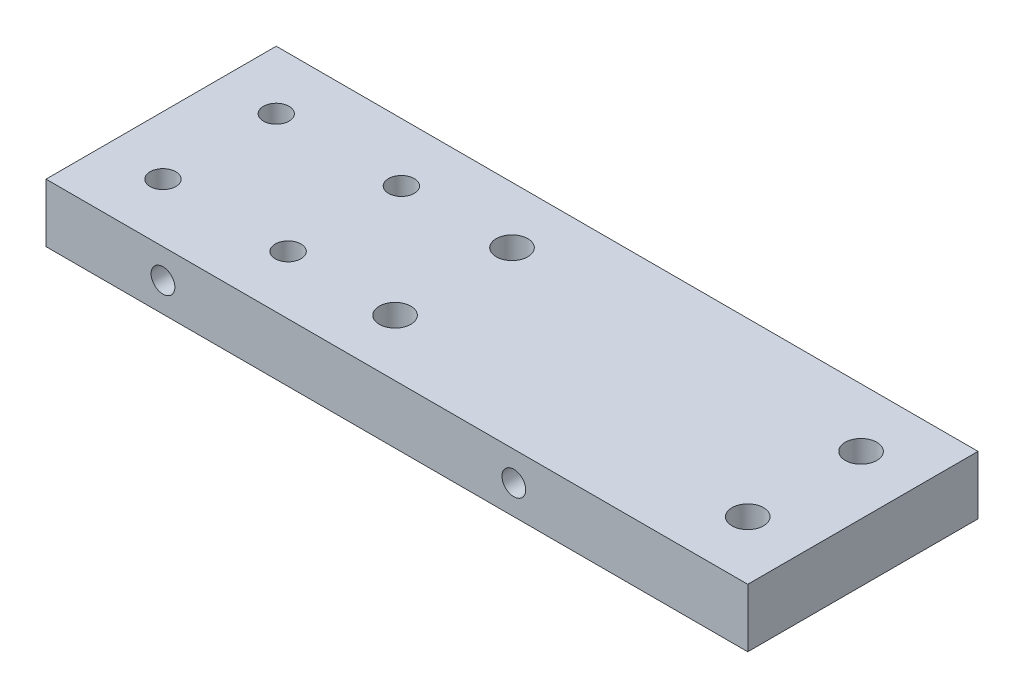
SolidWorks part; units mm, degrees
material "6061 Alloy"
ref_plane "Front Plane" through (0, 0, 0) normal (0, 0, 1) x (1, 0, 0)
ref_plane "Top Plane" through (0, 0, 0) normal (0, 1, 0) x (1, 0, 0)
ref_plane "Right Plane" through (0, 0, 0) normal (1, 0, 0) x (0, 0, -1)
sketch "Sketch1" plane through (0, 0, 0) normal (0, 1, 0) x (1, 0, 0)
  line L1 (-76.2, 25) -> (76.2, 25)
  line L2 (-76.2, 25) -> (-76.2, -25)
  line L3 (-76.2, -25) -> (76.2, -25)
  line L4 (76.2, 25) -> (76.2, -25)
  line L5 (-76.2, 25) -> (76.2, -25) construction
  line L6 (-76.2, -25) -> (76.2, 25) construction
  point P0 (0, 0)
  dimension "D1" = 50
  dimension "D2" = 152.4
extrude "Boss-Extrude1" add sketch "Sketch1" along normal blind 12.7
sketch "Sketch3" plane through (0, 0, 0) normal (0, -1, 0) x (1, 0, 0)
  line L0 (0, 0) -> (0, -20.7585) construction
  line L1 (0, 0) -> (-13.1006, 0) construction
  line L2 (-76.2, -25) -> (-76.2, 25) construction
  line L3 (-76.2, 25) -> (76.2, 25) construction
  line L4 (76.2, -25) -> (-76.2, -25) construction
  circle A0 centre (-63.5, 12.3) radius 2.794
  circle A1 centre (-63.5, -12.3) radius 2.794
  circle A2 centre (63.5, 12.3) radius 3.429
  circle A3 centre (63.5, -12.3) radius 3.429
  circle A4 centre (-12.699, 12.7) radius 3.429
  circle A5 centre (-12.699, -12.7) radius 3.429
  circle A6 centre (-36.322, 12.3) radius 2.794
  circle A7 centre (-36.322, -12.3) radius 2.794
  dimension "D1" = 12.7
  dimension "D4" = 76.2
  dimension "D5" = 76.2
  dimension "D6" = 27.178
  dimension "D7" = 27.178
  dimension "D8" = 5.588
  dimension "D9" = 5.588
  dimension "D10" = 5.588
  dimension "D11" = 5.588
  dimension "D12" = 6.858
  dimension "D13" = 6.858
  dimension "D14" = 6.858
  dimension "D15" = 6.858
  dimension "D2" = 12.7
  dimension "D3" = 12.7
extrude "Cut-Extrude2" cut sketch "Sketch3" against normal up to next
sketch "Sketch4" plane through (0, 0, 0) normal (0, -1, 0) x (1, 0, 0)
  circle A0 centre (-63.5, 12.3) radius 4.445
  circle A1 centre (-36.322, 12.3) radius 4.445
  circle A2 centre (-36.322, -12.3) radius 4.445
  circle A3 centre (-63.5, -12.3) radius 4.445
extrude "Cut-Extrude3" cut sketch "Sketch4" against normal blind 6.096
sketch "Sketch5" plane through (0, 0, -25) normal (0, 0, -1) x (-1, 0, 0)
  line L0 (-76.2, 12.7) -> (76.2, 12.7) construction
  line L1 (76.2, 12.7) -> (76.2, 0) construction
  line L2 (-76.2, 12.7) -> (-76.2, 0) construction
  circle A0 centre (50.8, 6.35) radius 2.5797
  circle A1 centre (-25.4, 6.35) radius 2.5797
  dimension "D1" = 6.35
  dimension "D3" = 6.35
  dimension "D4" = 50.8
  dimension "D5" = 5.1594
  dimension "D6" = 5.1594
  dimension "D2" = 25.4
extrude "Cut-Extrude4" cut sketch "Sketch5" against normal blind 12.7
sketch "Sketch6" plane through (0, 0, 25) normal (0, 0, 1) x (1, 0, 0)
  line L0 (-76.2, 12.7) -> (76.2, 12.7) construction
  line L1 (76.2, 12.7) -> (76.2, 0) construction
  line L2 (-76.2, 12.7) -> (-76.2, 0) construction
  circle A0 centre (25.4, 6.35) radius 2.5797
  circle A1 centre (-50.8, 6.35) radius 2.5797
  dimension "D1" = 6.35
  dimension "D3" = 25.4
  dimension "D4" = 6.35
  dimension "D5" = 5.1594
  dimension "D6" = 5.1594
  dimension "D2" = 50.8
extrude "Cut-Extrude5" cut sketch "Sketch6" against normal blind 12.7
